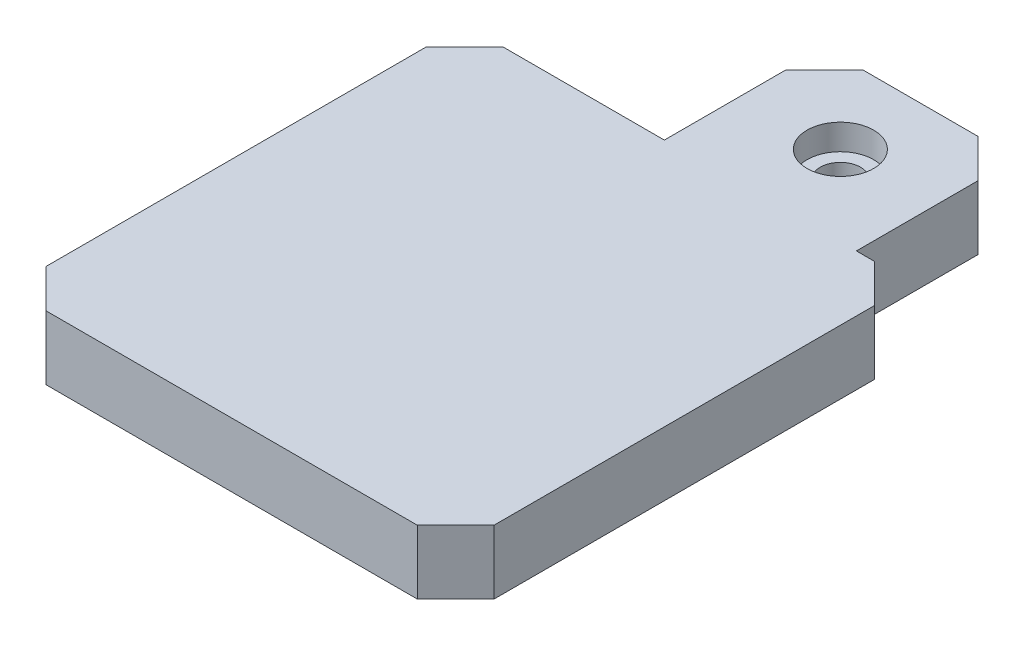
SolidWorks part; units mm, degrees
ref_plane "Front Plane" through (0, 0, 0) normal (0, 0, 1) x (1, 0, 0)
ref_plane "Top Plane" through (0, 0, 0) normal (0, 1, 0) x (1, 0, 0)
ref_plane "Right Plane" through (0, 0, 0) normal (1, 0, 0) x (0, 0, -1)
sketch "Sketch1" plane through (0, 0, 0) normal (0, 1, 0) x (1, 0, 0)
  line L0 (0, 17.5) -> (0, 30) construction
  line L1 (-17.5, -17.5) -> (17.5, -17.5)
  line L2 (-17.5, -17.5) -> (-17.5, 17.5)
  line L3 (-17.5, 17.5) -> (17.5, 17.5)
  line L4 (17.5, -17.5) -> (17.5, 17.5)
  line L5 (-17.5, -17.5) -> (17.5, 17.5) construction
  line L6 (-17.5, 17.5) -> (17.5, -17.5) construction
  line L7 (7.5, 17.5) -> (-7.5, 17.5) construction
  line L8 (-7.5, 17.5) -> (-7.5, 30) construction
  line L9 (7.5, 17.5) -> (7.5, 30)
  line L10 (7.5, 30) -> (-1.9, 30)
  line L11 (7.5, 17.5) -> (13.1, 17.5) construction
  line L12 (13.1, 17.5) -> (13.1, 30)
  line L13 (13.1, 30) -> (7.5, 30)
  line L14 (-7.5, 17.5) -> (-1.9, 17.5) construction
  line L15 (-1.9, 17.5) -> (-1.9, 30)
  line L16 (13.1, 23.75) -> (-1.9, 23.75) construction
  line L17 (-17.5, -17.5) -> (-17.5, -18.2)
  line L18 (-17.5, -18.2) -> (17.5, -18.2)
  line L19 (17.5, -18.2) -> (17.5, -17.5)
  circle A1 centre (0, 23.75) radius 2.5 construction
  circle A2 centre (5.6, 23.75) radius 2.6
  point P0 (0, 0)
  point P11 (0, 17.5)
  dimension "D3" = 5
  dimension "D7" = 5.2
  dimension "D1" = 35
  dimension "D2" = 12.5
  dimension "D4" = 7.5
  dimension "D5" = 5.6
  dimension "D6" = 5.6
  dimension "D8" = 0.7
extrude "Boss-Extrude1" add sketch "Sketch1" along normal blind 5 contours A2 L9 L3 L12 L13 | A2 L9 L10 L15 L3 | L18 L19 L1 L17 | L1 L4 L3 L2 region at (0, 0, 0) region at (0, 0, 17.85) region at (2.2799, 0, -23.75) region at (10.3629, 0, -23.75)
chamfer "Chamfer1" distance 3 angle 45 6 edges at (13.1, 2.5, -30) (-1.9, 2.5, -30) (17.5, 2.5, 18.2) (17.5, 2.5, -17.5) (-17.5, 2.5, 18.2) (-17.5, 2.5, -17.5)
ref_plane "Plane2" through (0, 2, 0) normal (0, 1, 0) x (1, 0, 0)
sketch "Sketch4" plane through (0, 2, 0) normal (0, 1, 0) x (1, 0, 0)
  circle A0 centre (5.6, 23.75) radius 2.6
  circle A1 centre (5.6, 23.75) radius 1.58
  dimension "D1" = 5.2
  dimension "D2" = 3.16
extrude "Boss-Extrude2" add sketch "Sketch4" along normal blind 1
